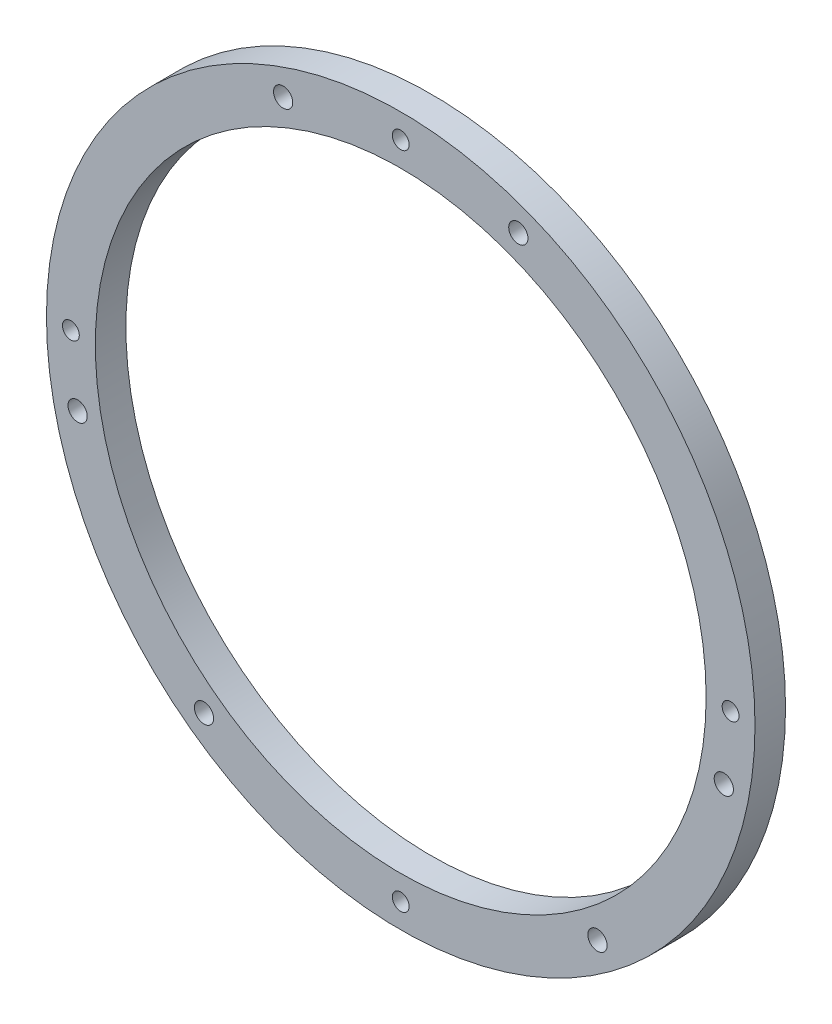
SolidWorks part; units mm, degrees
material "ABS"
ref_plane "Front Plane" through (0, 0, 0) normal (0, 0, 1) x (1, 0, 0)
ref_plane "Top Plane" through (0, 0, 0) normal (0, 1, 0) x (1, 0, 0)
ref_plane "Right Plane" through (0, 0, 0) normal (1, 0, 0) x (0, 0, -1)
sketch "Sketch2" plane through (0, 0, -69.215) normal (0, 0, 1) x (1, 0, 0)
  line L0 (0, 68.58) -> (0, 0) construction
  line L1 (-57.8398, -36.848) -> (0, 0) construction
  line L2 (0, 0) -> (57.8398, -36.848) construction
  line L3 (0, 0) -> (0, -68.58) construction
  line L4 (-24.45, 64.0735) -> (24.45, 64.0735) construction
  line L5 (-67.176, -13.8058) -> (-40.9021, -55.0476) construction
  line L6 (40.9021, -55.0476) -> (67.176, -13.8058) construction
  circle A0 centre (0, 0) radius 74.93 construction
  circle A1 centre (0, 0) radius 63.5 construction
  circle A2 centre (0, -68.58) radius 1.25 construction
  circle A3 centre (68.58, 0) radius 1.25 construction
  circle A4 centre (0, 68.58) radius 1.25 construction
  circle A5 centre (-68.58, 0) radius 1.25 construction
  circle A6 centre (0, 0) radius 74.93 construction
  circle A7 centre (0, 0) radius 63.5
  circle A8 centre (0, -68.58) radius 1.25 construction
  circle A9 centre (68.58, 0) radius 1.25 construction
  circle A10 centre (0, 68.58) radius 1.25 construction
  circle A11 centre (-68.58, 0) radius 1.25 construction
  circle A12 centre (-68.58, 0) radius 1.75
  circle A13 centre (0, 68.58) radius 1.75
  circle A14 centre (68.58, 0) radius 1.75
  circle A15 centre (0, -68.58) radius 1.75
  circle A16 centre (0, 68.58) radius 5.08 construction
  circle A17 centre (0, 0) radius 73.66
  circle A18 centre (0, 0) radius 68.58 construction
  circle A19 centre (-24.45, 64.0735) radius 2
  circle A20 centre (24.45, 64.0735) radius 2
  circle A21 centre (-67.176, -13.8058) radius 2
  circle A22 centre (-40.9021, -55.0476) radius 2
  circle A23 centre (40.9021, -55.0476) radius 2
  circle A24 centre (67.176, -13.8058) radius 2
  dimension "D1" = 3.5
  dimension "D2" = 4
  dimension "D3" = 50
  dimension "D4" = 57.5
extrude "Boss-Extrude1" add sketch "Sketch2" along normal blind 6.35
